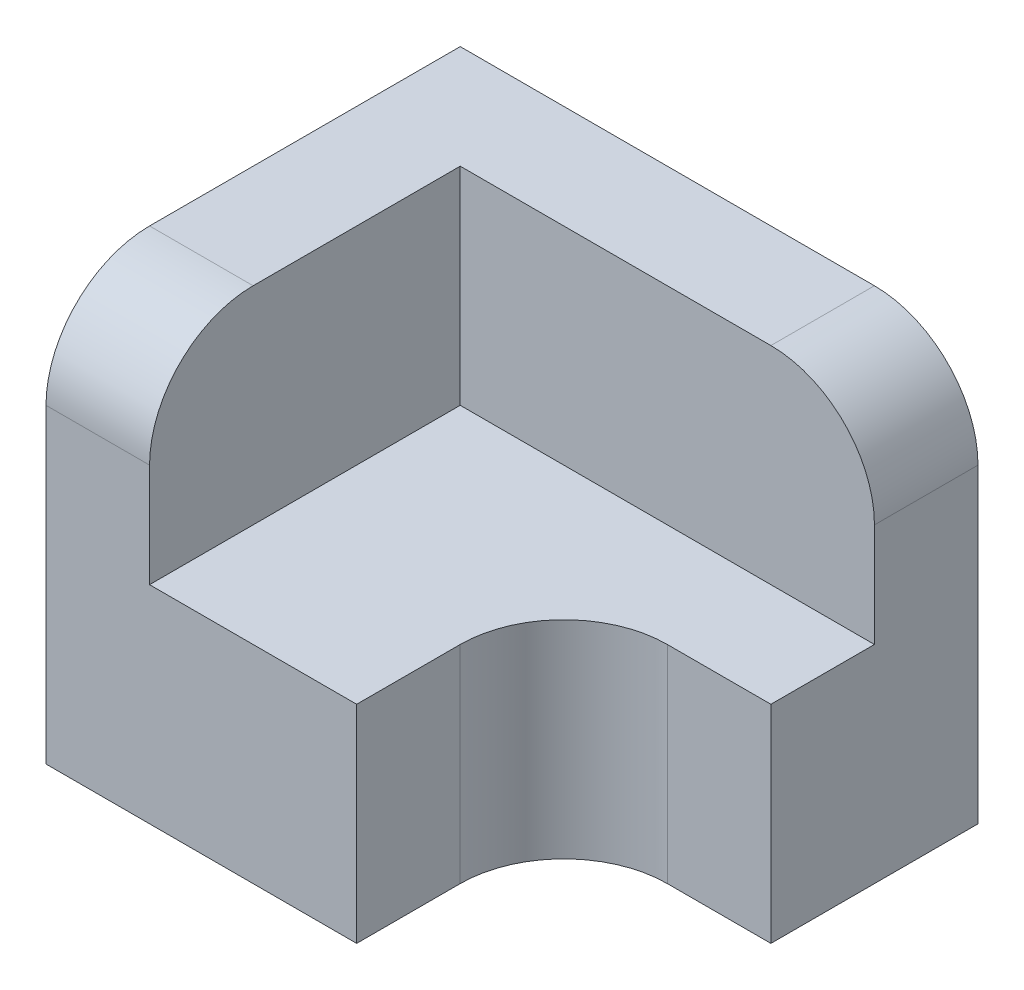
SolidWorks part; units mm, degrees
ref_plane "前基準面" through (0, 0, 0) normal (0, 0, 1) x (1, 0, 0)
ref_plane "上基準面" through (0, 0, 0) normal (0, 1, 0) x (1, 0, 0)
ref_plane "右基準面" through (0, 0, 0) normal (1, 0, 0) x (0, 0, -1)
sketch "草圖1" plane through (0, 0, 0) normal (0, 1, 0) x (1, 0, 0)
  line L1 (-12.5, -10) -> (12.5, -10)
  line L2 (-12.5, -10) -> (-12.5, 10)
  line L3 (-12.5, 10) -> (12.5, 10)
  line L4 (12.5, -10) -> (12.5, 10)
  line L5 (-12.5, -10) -> (12.5, 10) construction
  line L6 (-12.5, 10) -> (12.5, -10) construction
  line L7 (-12.5, -10) -> (-7.5, -10)
  line L8 (-12.5, -10) -> (-12.5, 10)
  line L9 (-12.5, 10) -> (-7.5, 10)
  line L10 (-7.5, -10) -> (-7.5, 5)
  line L11 (-12.5, 10) -> (12.5, 10)
  line L12 (-12.5, 10) -> (-12.5, 5)
  line L13 (-7.5, 5) -> (12.5, 5)
  line L14 (12.5, 10) -> (12.5, 5)
  line L15 (12.5, -10) -> (2.5, -10)
  line L16 (12.5, -10) -> (12.5, 0)
  line L17 (12.5, 0) -> (7.5, 0)
  line L18 (2.5, -10) -> (2.5, -5)
  arc A0 (2.5, -5) -> (7.5, 0) centre (7.5, -5) cw
  point P0 (0, 0)
  dimension "D7" = 5
  dimension "D1" = 20
  dimension "D2" = 25
  dimension "D3" = 5
  dimension "D4" = 5
  dimension "D5" = 5
  dimension "D6" = 10
extrude "填料-伸長1" add sketch "草圖1" along normal blind 10 contours L18 A0 L17 L4 L13 L10 L1 | L10 L13 L4 L3 L8 L2 L1 region at (-12.1798, 0, 2.5) region at (0.0945, 0, 1.2465)
extrude "填料-伸長2" add sketch "草圖1<3>" along normal blind 20 contours L10 L13 L4 L3 L8 L2 L1 region at (-12.1798, 0, 2.5)
sketch "草圖1<3>" plane through (0, 0, 0) normal (0, 1, 0) x (1, 0, 0) same geometry as "草圖1"
fillet "圓角1" radius 5 2 edges at (-10, 20, 10) (12.5, 20, -7.5)
scale "縮放比例1" scale about centroid uniform scaling yes scale factor 0.2
